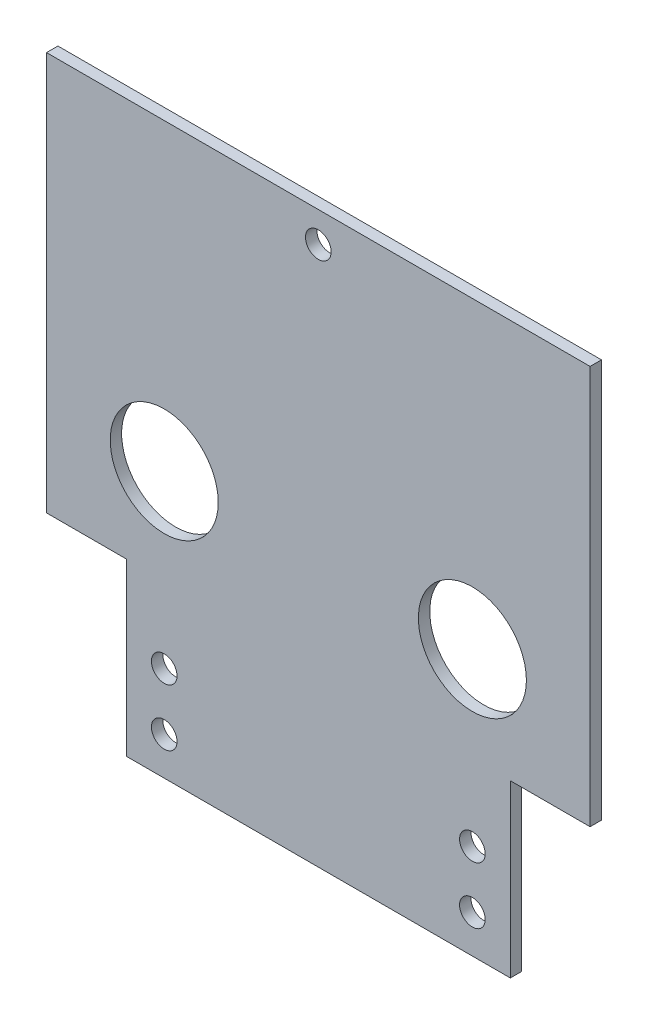
SolidWorks part; units mm, degrees
ref_plane "Front Plane" through (0, 0, 0) normal (0, 0, 1) x (1, 0, 0)
ref_plane "Top Plane" through (0, 0, 0) normal (0, 1, 0) x (1, 0, 0)
ref_plane "Right Plane" through (0, 0, 0) normal (1, 0, 0) x (0, 0, -1)
sketch "Sketch1" plane through (0, 0, 0) normal (0, 0, 1) x (1, 0, 0)
  line L1 (0, 0) -> (143.16, 0)
  line L2 (0, 0) -> (0, -150)
  line L3 (0, -150) -> (143.16, -150)
  line L4 (143.16, 0) -> (143.16, -150)
  dimension "D1" = 150
  dimension "D2" = 143.16
extrude "Boss-Extrude1" add sketch "Sketch1" along normal blind 3
sketch "Sketch2" plane through (0, 0, 3) normal (0, 0, 1) x (1, 0, 0)
  line L0 (0, 0) -> (0, -150) construction
  line L1 (143.16, -150) -> (143.16, 0) construction
  line L2 (0, -150) -> (143.16, -150) construction
  line L3 (143.16, 0) -> (0, 0) construction
  line L4 (143.16, 0) -> (0, 0) construction
  circle A0 centre (31, -80) radius 14.225
  circle A1 centre (112.16, -80) radius 14.225
  circle A3 centre (31, -140) radius 3.375
  circle A4 centre (112.16, -140) radius 3.375
  circle A7 centre (71.58, -8) radius 3.375
  circle A8 centre (31, -125) radius 3.375
  circle A9 centre (112.16, -125) radius 3.375
  point P10 (0, 0)
  point P13 (71.58, 0)
  dimension "D1" = 28.45
  dimension "D2" = 28.45
  dimension "D3" = 10
  dimension "D4" = 6.75
  dimension "D5" = 6.75
  dimension "D7" = 6.75
  dimension "D14" = 6.75
  dimension "D17" = 6.75
  dimension "D9" = 31
  dimension "D10" = 31
  dimension "D12" = 80
  dimension "D13" = 8
  dimension "D15" = 15
  dimension "D16" = 15
extrude "Cut-Extrude1" cut sketch "Sketch2" against normal through all
sketch "Sketch3" plane through (0, 0, 0) normal (0, 0, -1) x (-1, 0, 0)
  line L0 (-39.2577, -150) -> (-39.2577, -98)
  line L1 (0, -150) -> (-143.16, -150) construction
  line L2 (-39.2577, -98) -> (-48.7877, -98)
  line L3 (-48.7877, -98) -> (-48.7877, -150)
  line L4 (-48.7877, -150) -> (-39.2577, -150)
  line L5 (-103.5592, -150) -> (-103.5592, -98)
  line L6 (-103.5592, -98) -> (-94.0342, -98)
  line L7 (-94.0342, -98) -> (-94.0342, -150)
  line L8 (-94.0342, -150) -> (-103.5592, -150)
  dimension "D1" = 52
  dimension "D2" = 52
  dimension "D3" = 9.525
  dimension "D4" = 9.53
sketch "Sketch4" plane through (0, 0, 3) normal (0, 0, 1) x (1, 0, 0)
  line L1 (21, -150) -> (21, -105)
  line L2 (21, -105) -> (0, -105)
  line L3 (0, 0) -> (0, -150) construction
  line L4 (0, -105) -> (0, -150)
  line L5 (0, -150) -> (21, -150)
  line L6 (0, -150) -> (143.16, -150) construction
  line L8 (143.16, -150) -> (122.16, -150)
  line L9 (143.16, -150) -> (143.16, -105)
  line L10 (143.16, -105) -> (122.16, -105)
  line L11 (122.16, -150) -> (122.16, -105)
  dimension "D1" = 45
  dimension "D2" = 21
  dimension "D3" = 21
  dimension "D4" = 45
extrude "Cut-Extrude3" cut sketch "Sketch4" against normal through all
